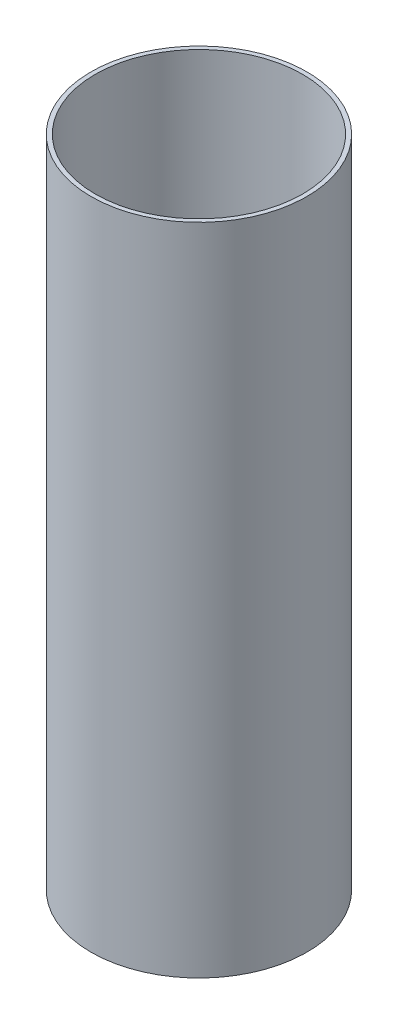
SolidWorks part; units mm, degrees
ref_plane "Front Plane" through (0, 0, 0) normal (0, 0, 1) x (1, 0, 0)
ref_plane "Top Plane" through (0, 0, 0) normal (0, 1, 0) x (1, 0, 0)
ref_plane "Right Plane" through (0, 0, 0) normal (1, 0, 0) x (0, 0, -1)
sketch "Sketch1" plane through (0, 0, 0) normal (0, 1, 0) x (1, 0, 0)
  circle A0 centre (0, 0) radius 36.45
  circle A1 centre (0, 0) radius 37.95
  dimension "D1" = 72.9
  dimension "D2" = 75.9
extrude "Boss-Extrude1" add sketch "Sketch1" along normal blind 115 and the other way blind 115
